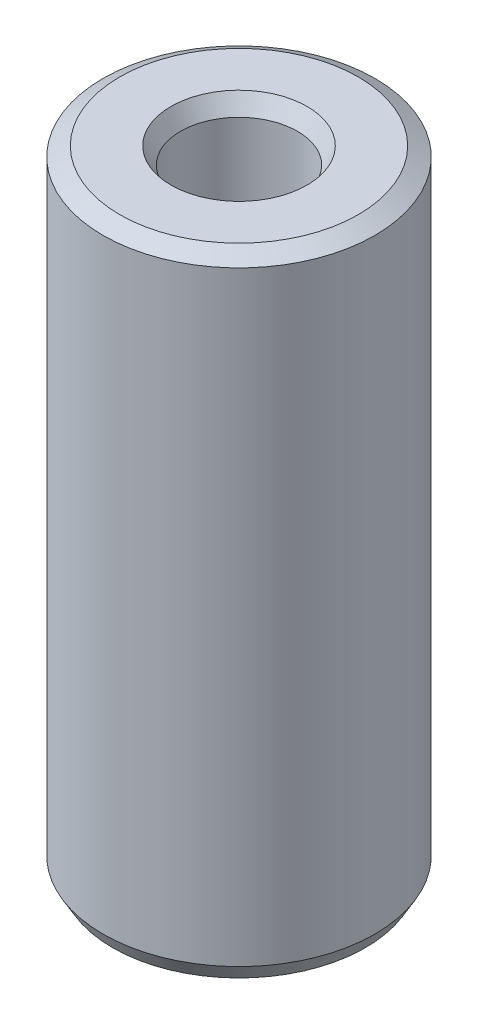
SolidWorks part; units mm, degrees
ref_plane "Front Plane" through (0, 0, 0) normal (0, 0, 1) x (1, 0, 0)
ref_plane "Top Plane" through (0, 0, 0) normal (0, 1, 0) x (1, 0, 0)
ref_plane "Right Plane" through (0, 0, 0) normal (1, 0, 0) x (0, 0, -1)
sketch "Sketch1" plane through (0, 0, 0) normal (0, 1, 0) x (1, 0, 0)
  circle A0 centre (0, 0) radius 27.5
  dimension "SLEEVE_OD" = 55
extrude "Boss-Extrude1" add sketch "Sketch1" along normal blind 127.7066
sketch "Sketch2" plane through (0, 0, 0) normal (0, 1, 0) x (1, 0, 0)
  circle A0 centre (0, 0) radius 11.8312
  dimension "BORE_D" = 23.6623
extrude "Cut-Extrude1" cut sketch "Sketch2" along normal through all
chamfer "Chamfer1" distance 1.9471 angle 60 4 edges at (0, 127.7066, 11.8312) (0, 0, 11.8312) (0, 0, 27.5) (0, 127.7066, 27.5) first distance on face at (0, 127.7066, 11.8312) first distance on face at (0, 0, 11.8312) first distance on face at (0, 127.7066, 27.5)
